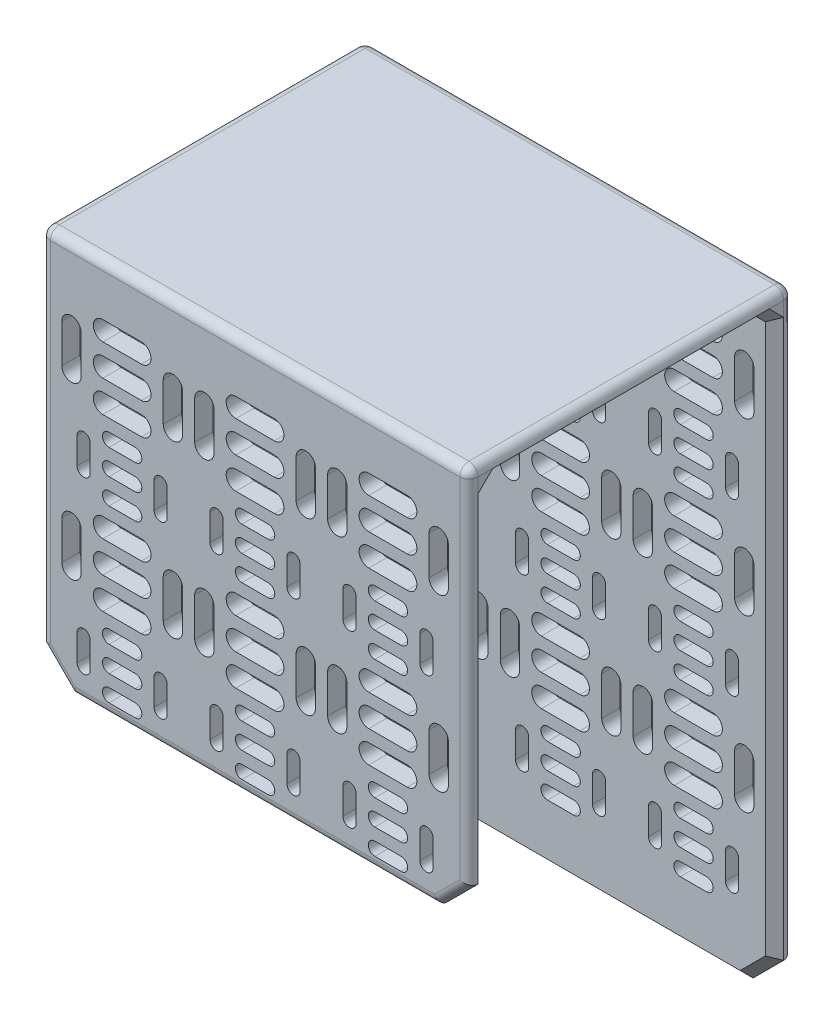
SolidWorks part; units mm, degrees
ref_plane "XY" through (0, 0, 0) normal (0, 0, 1) x (1, 0, 0)
ref_plane "-XZ" through (0, 0, 0) normal (0, 1, 0) x (1, 0, 0)
ref_plane "ZY" through (0, 0, 0) normal (1, 0, 0) x (0, 0, -1)
sketch "Esquisse1" plane through (0, 0, 0) normal (0, 0, 1) x (1, 0, 0)
  line L5 (-35, -50) -> (35, -50)
  line L6 (-35, -50) -> (-35, 50)
  line L7 (-35, 50) -> (35, 50)
  line L8 (35, -50) -> (35, 50)
  line L9 (-35, -50) -> (35, 50) construction
  line L10 (-35, 50) -> (35, -50) construction
  point P0 (0, 0)
  dimension "D1" = 100
  dimension "D2" = 70
extrude "Boss.-Extru.1" add sketch "Esquisse1" along normal blind 3
sketch "Esquisse2" plane through (0, 0, 3) normal (0, 0, 1) x (1, 0, 0)
  line L0 (-35, 50) -> (35, 50)
  line L1 (35, 50) -> (-35, 50) construction
  line L2 (-35, 50) -> (-35, 47)
  line L3 (-35, 47) -> (35, 47)
  line L4 (35, 47) -> (35, 50)
  line L7 (-35, 50) -> (-35, -50) construction
  point P5 (0, 50)
  dimension "D1" = 70
  dimension "D2" = 3
extrude "Boss.-Extru.2" add sketch "Esquisse2" along normal blind 50
sketch "Esquisse3" plane through (0, 47, 0) normal (0, -1, 0) x (1, 0, 0)
  line L0 (35, 53) -> (35, 3) construction
  line L1 (-35, 53) -> (35, 53)
  line L2 (-35, 53) -> (-35, 50)
  line L3 (-35, 50) -> (35, 50)
  line L4 (35, 53) -> (35, 50)
  line L5 (-35, 53) -> (-35, 3) construction
  line L6 (-35, 53) -> (35, 53) construction
  dimension "D1" = 3
extrude "Boss.-Extru.3" add sketch "Esquisse3" along normal blind 61.2
sketch "Esquisse4" plane through (0, 0, 3) normal (0, 0, 1) x (1, 0, 0)
  line L0 (-3.15, 6.975) -> (3.15, 6.975) construction
  line L1 (8.3, 3.825) -> (8.3, 10.125) construction
  line L3 (-3.15, 8.55) -> (3.15, 8.55)
  line L4 (-3.15, 5.4) -> (3.15, 5.4)
  line L5 (9.875, 10.125) -> (9.875, 3.825)
  line L6 (6.725, 10.125) -> (6.725, 3.825)
  line L7 (-8.3, 6.975) -> (8.3, 6.975) construction
  line L8 (0, 5.4) -> (0, 8.55) construction
  line L9 (-6.725, 10.125) -> (-6.725, 3.825)
  line L10 (-9.875, 10.125) -> (-9.875, 3.825)
  line L11 (-2.15, -6.975) -> (2.15, -6.975) construction
  line L12 (6.3, -9.125) -> (6.3, -4.825) construction
  line L13 (-2.15, -5.9) -> (2.15, -5.9)
  line L14 (-2.15, -8.05) -> (2.15, -8.05)
  line L15 (7.375, -4.825) -> (7.375, -9.125)
  line L16 (5.225, -4.825) -> (5.225, -9.125)
  line L17 (-6.3, -6.975) -> (6.3, -6.975) construction
  line L18 (0, -8.05) -> (0, -5.9) construction
  line L19 (-5.225, -4.825) -> (-5.225, -9.125)
  line L20 (-7.375, -4.825) -> (-7.375, -9.125)
  line L21 (0, 6.975) -> (0, -6.975) construction
  line L23 (-3.15, 13.7) -> (3.15, 13.7)
  line L24 (-3.15, 10.55) -> (3.15, 10.55)
  line L25 (-3.15, 3.4) -> (3.15, 3.4)
  line L26 (-3.15, 0.25) -> (3.15, 0.25)
  line L27 (-2.15, -1.75) -> (2.15, -1.75)
  line L28 (-2.15, -3.9) -> (2.15, -3.9)
  line L29 (-2.15, -10.05) -> (2.15, -10.05)
  line L30 (-2.15, -12.2) -> (2.15, -12.2)
  line L31 (-35, 47) -> (35, 47) construction
  arc A11 (8.3, 8.55) -> (6.725, 6.975) centre (8.3, 6.975) ccw construction
  arc A13 (9.875, 10.125) -> (6.725, 10.125) centre (8.3, 10.125) ccw
  arc A14 (6.725, 3.825) -> (9.875, 3.825) centre (8.3, 3.825) ccw
  arc A15 (0, 5.4) -> (1.575, 6.975) centre (0, 6.975) ccw
  arc A16 (3.15, 5.4) -> (3.15, 8.55) centre (3.15, 6.975) ccw
  arc A17 (-3.15, 8.55) -> (-3.15, 5.4) centre (-3.15, 6.975) ccw
  arc A18 (-1.575, 6.975) -> (-3.15, 8.55) centre (-3.15, 6.975) ccw construction
  arc A19 (0, 8.55) -> (-1.575, 6.975) centre (0, 6.975) ccw construction
  arc A20 (1.575, 6.975) -> (0, 8.55) centre (0, 6.975) ccw construction
  arc A21 (3.15, 8.55) -> (1.575, 6.975) centre (3.15, 6.975) ccw construction
  arc A22 (-3.15, 5.4) -> (-1.575, 6.975) centre (-3.15, 6.975) ccw construction
  arc A23 (-1.575, 6.975) -> (0, 5.4) centre (0, 6.975) ccw construction
  arc A24 (1.575, 6.975) -> (3.15, 5.4) centre (3.15, 6.975) ccw construction
  arc A25 (8.3, 8.55) -> (9.875, 10.125) centre (8.3, 10.125) ccw construction
  arc A26 (9.875, 6.975) -> (8.3, 8.55) centre (8.3, 6.975) ccw construction
  arc A27 (8.3, 5.4) -> (9.875, 6.975) centre (8.3, 6.975) ccw construction
  arc A28 (9.875, 3.825) -> (8.3, 5.4) centre (8.3, 3.825) ccw construction
  arc A29 (8.3, 5.4) -> (6.725, 3.825) centre (8.3, 3.825) ccw construction
  arc A30 (6.725, 6.975) -> (8.3, 5.4) centre (8.3, 6.975) ccw construction
  arc A31 (6.725, 10.125) -> (8.3, 8.55) centre (8.3, 10.125) ccw construction
  arc A32 (-9.875, 10.125) -> (-6.725, 10.125) centre (-8.3, 10.125) cw
  arc A33 (-6.725, 3.825) -> (-9.875, 3.825) centre (-8.3, 3.825) cw
  arc A34 (6.3, -5.9) -> (5.225, -6.975) centre (6.3, -6.975) ccw construction
  arc A35 (7.375, -4.825) -> (5.225, -4.825) centre (6.3, -4.825) ccw
  arc A36 (5.225, -9.125) -> (7.375, -9.125) centre (6.3, -9.125) ccw
  arc A37 (0, -8.05) -> (1.075, -6.975) centre (0, -6.975) ccw
  arc A38 (2.15, -8.05) -> (2.15, -5.9) centre (2.15, -6.975) ccw
  arc A39 (-2.15, -5.9) -> (-2.15, -8.05) centre (-2.15, -6.975) ccw
  arc A40 (-1.075, -6.975) -> (-2.15, -5.9) centre (-2.15, -6.975) ccw construction
  arc A41 (0, -5.9) -> (-1.075, -6.975) centre (0, -6.975) ccw construction
  arc A42 (1.075, -6.975) -> (0, -5.9) centre (0, -6.975) ccw construction
  arc A43 (2.15, -5.9) -> (1.075, -6.975) centre (2.15, -6.975) ccw construction
  arc A44 (-2.15, -8.05) -> (-1.075, -6.975) centre (-2.15, -6.975) ccw construction
  arc A45 (-1.075, -6.975) -> (0, -8.05) centre (0, -6.975) ccw construction
  arc A46 (1.075, -6.975) -> (2.15, -8.05) centre (2.15, -6.975) ccw construction
  arc A47 (6.3, -5.9) -> (7.375, -4.825) centre (6.3, -4.825) ccw construction
  arc A48 (7.375, -6.975) -> (6.3, -5.9) centre (6.3, -6.975) ccw construction
  arc A49 (6.3, -8.05) -> (7.375, -6.975) centre (6.3, -6.975) ccw construction
  arc A50 (7.375, -9.125) -> (6.3, -8.05) centre (6.3, -9.125) ccw construction
  arc A51 (6.3, -8.05) -> (5.225, -9.125) centre (6.3, -9.125) ccw construction
  arc A52 (5.225, -6.975) -> (6.3, -8.05) centre (6.3, -6.975) ccw construction
  arc A53 (5.225, -4.825) -> (6.3, -5.9) centre (6.3, -4.825) ccw construction
  arc A54 (-7.375, -4.825) -> (-5.225, -4.825) centre (-6.3, -4.825) cw
  arc A55 (-5.225, -9.125) -> (-7.375, -9.125) centre (-6.3, -9.125) cw
  arc A56 (3.15, 10.55) -> (3.15, 13.7) centre (3.15, 12.125) ccw
  arc A57 (-3.15, 13.7) -> (-3.15, 10.55) centre (-3.15, 12.125) ccw
  arc A58 (-3.15, 0.25) -> (-3.15, 3.4) centre (-3.15, 1.825) cw
  arc A59 (3.15, 3.4) -> (3.15, 0.25) centre (3.15, 1.825) cw
  arc A60 (2.15, -3.9) -> (2.15, -1.75) centre (2.15, -2.825) ccw
  arc A61 (-2.15, -1.75) -> (-2.15, -3.9) centre (-2.15, -2.825) ccw
  arc A62 (-2.15, -12.2) -> (-2.15, -10.05) centre (-2.15, -11.125) cw
  arc A63 (2.15, -10.05) -> (2.15, -12.2) centre (2.15, -11.125) cw
  point P6 (8.3, 6.975)
  point P10 (0, 6.975)
  point P26 (0, 6.975)
  point P44 (6.3, -6.975)
  point P48 (0, -6.975)
  point P64 (0, -6.975)
  dimension "D3" = 3.15
  dimension "D1" = 2.15
  dimension "D2" = 5.15
  dimension "D4" = 4.15
  dimension "D5" = 2
  dimension "D9" = 19.75
  dimension "D6" = 2
  dimension "D10" = 2
  dimension "D11" = 25.9
  dimension "D12" = 59.2
  dimension "D7" = 2
  dimension "D8" = 2
extrude "Enlèv. mat.-Extru.1" cut sketch "Esquisse4" against normal through all both and the other way through all
pattern_linear "Répétition linéaire1" count 2 spacing 27.9 along (0, -1, 0) count 2 spacing 27.9 along (0, 1, 0) of "Enlèv. mat.-Extru.1"
pattern_linear "Répétition linéaire2" count 2 spacing 21.75 along (-1, 0, 0) count 2 spacing 21.75 along (1, 0, 0) of "Répétition linéaire1", "Enlèv. mat.-Extru.1"
chamfer "Chanfrein1" distance 1.5 angle 45 2 edges at (0, 47, 50) (0, 47, 3)
chamfer "Chanfrein2" distance 5 angle 45 4 edges at (35, -14.2, 51.5) (-35, -14.2, 51.5) (35, -50, 1.5) (-35, -50, 1.5)
chamfer "Chanfrein3" distance 1.5 angle 45 16 edges at (35, 0.25, 3) (-35, 47, 26.5) (35, 47, 26.5) (-35, 18.15, 50) (-32.5, -11.7, 50) (0, -14.2, 50) (32.5, -11.7, 50) (35, 18.15, 50) (35, 46.25, 49.25) (-35, 46.25, 49.25) (35, 46.25, 3.75) (-35, 46.25, 3.75) (-35, 0.25, 3) (-32.5, -47.5, 3) (0, -50, 3) (32.5, -47.5, 3)
fillet "Congé1" radius 1.5 15 edges at (0, 50, 0) (35, 2.5, 0) (0, -50, 0) (-35, 2.5, 0) (0, 50, 53) (35, 50, 26.5) (32.5, -47.5, 0) (-32.5, -47.5, 0) (-35, 50, 26.5) (-35, 20.4, 53) (-32.5, -11.7, 53) (0, -14.2, 53) (32.5, -11.7, 53) (35, 20.4, 53) (-33.5, 18.4607, 50)
equation "\"D2@Esquisse4\" = \"D3@Esquisse4\" + 2"
equation "\"D4@Esquisse4\" = \"D1@Esquisse4\" + 2"
equation "\"D6@Esquisse4\" = \"D5@Esquisse4\""
equation "\"D10@Esquisse4\" = \"D5@Esquisse4\""
equation "\"D3@Répétition linéaire1\"=\"D11@Esquisse4\"+2"
equation "\"D3@Répétition linéaire2\"=\"D9@Esquisse4\"+2"
equation "\"D1@Boss.-Extru.3\"=\"D12@Esquisse4\"+2"
